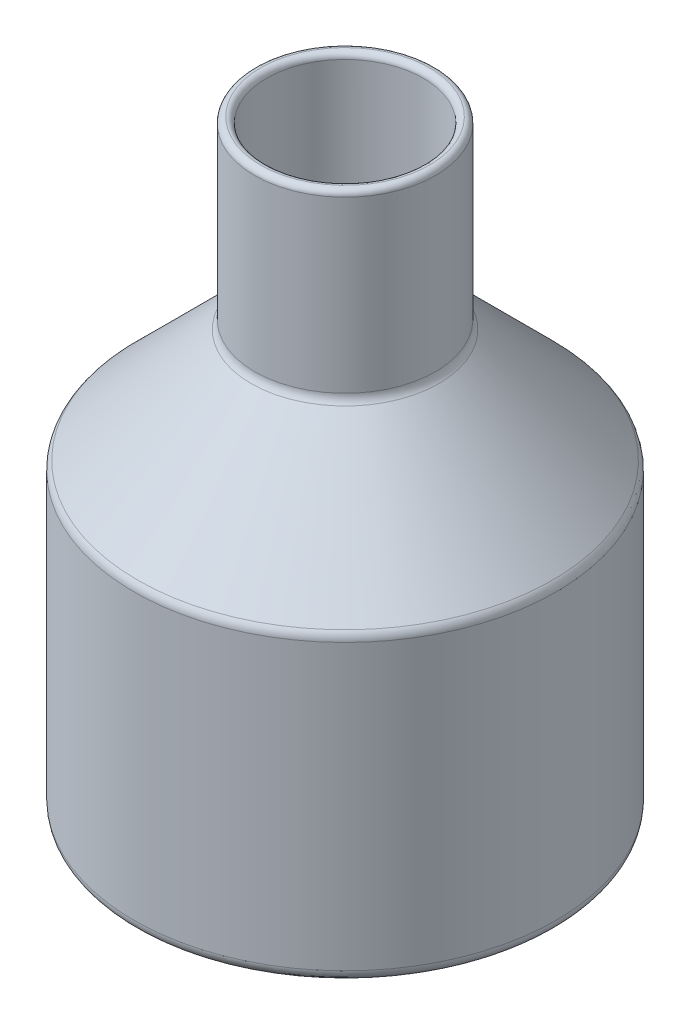
SolidWorks part; units mm, degrees
ref_plane "정면" through (0, 0, 0) normal (0, 0, 1) x (1, 0, 0)
ref_plane "윗면" through (0, 0, 0) normal (0, 1, 0) x (1, 0, 0)
ref_plane "우측면" through (0, 0, 0) normal (1, 0, 0) x (0, 0, -1)
sketch "스케치1" plane through (0, 0, 0) normal (0, 0, 1) x (1, 0, 0)
  line L0 (-11.8631, 50.3256) -> (-11.8631, -75.5348) construction
  line L1 (-11.8631, -69.9739) -> (-46.8631, -69.9739)
  line L2 (-46.8631, -69.9739) -> (-46.8631, -19.9739)
  line L3 (-46.8631, -19.9739) -> (-26.8631, 0.0261)
  line L4 (-26.8631, 0.0261) -> (-26.8631, 30.0261)
  line L5 (-26.8631, 30.0261) -> (-24.8631, 30.0261)
  line L6 (-11.8631, -67.9739) -> (-44.8631, -67.9739)
  line L7 (-44.8631, -67.9739) -> (-44.8631, -20.8023)
  line L8 (-44.8631, -20.8023) -> (-24.8631, -0.8023)
  line L9 (-24.8631, -0.8023) -> (-24.8631, 28.0261)
  line L11 (-24.8631, 28.0261) -> (-24.8631, 30.0261)
  line L12 (-24.8631, 28.0261) -> (-11.8631, 28.0261) construction
  line L13 (-26.8631, 30.0261) -> (-11.8631, 30.0261) construction
  line L14 (-11.8631, -67.9739) -> (-11.8631, -69.9739)
  dimension "D1" = 50
  dimension "D2" = 70
  dimension "D3" = 30
  dimension "D4" = 20
  dimension "D5" = 30
  dimension "D6" = 2
revolve "회전1" add sketch "스케치1" angle 360 about L0
fillet "필렛3" radius 2 5 edges at (-11.8631, -0.8023, 13) (-11.8631, -20.8023, 33) (-11.8631, -67.9739, 33) (-11.8631, -19.9739, 35) (-11.8631, 0.0261, 15)
fillet "필렛4" radius 1 2 edges at (-11.8631, 30.0261, 15) (-11.8631, 30.0261, 13)
fillet "필렛5" radius 2 1 edges at (-11.8631, -69.9739, 35)
